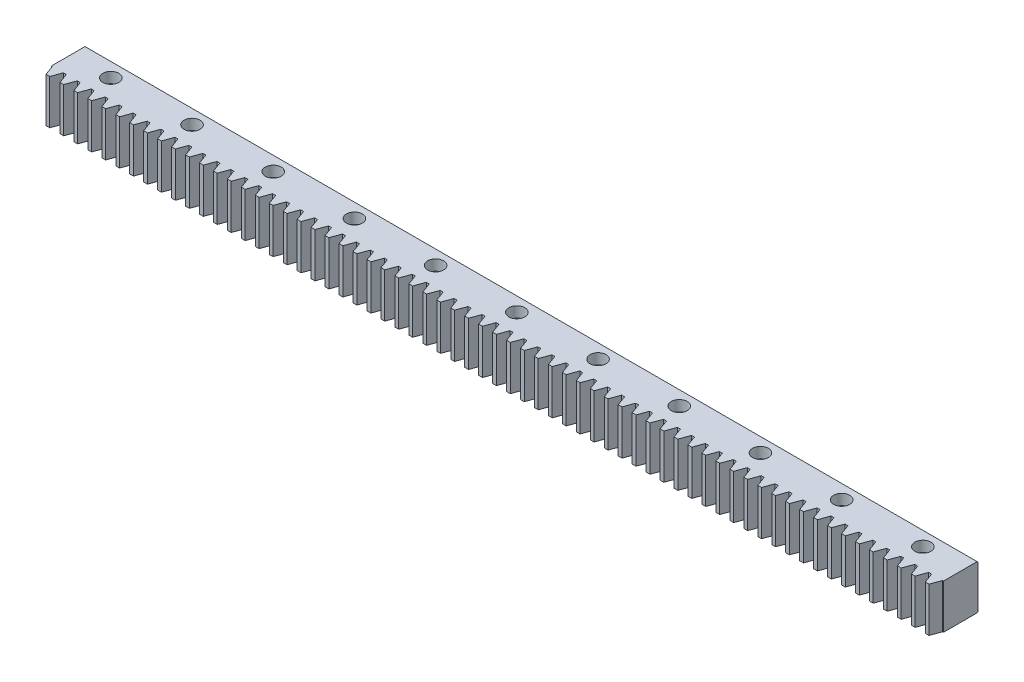
SolidWorks part; units mm, degrees
ref_plane "前基準面" through (0, 0, 0) normal (0, 0, 1) x (1, 0, 0)
ref_plane "上基準面" through (0, 0, 0) normal (0, 1, 0) x (1, 0, 0)
ref_plane "右基準面" through (0, 0, 0) normal (1, 0, 0) x (0, 0, -1)
sketch "草圖1" plane through (0, 0, 0) normal (0, 1, 0) x (1, 0, 0)
  line L1 (-502, 0) -> (502, 0)
  line L2 (-502, 0) -> (-502, -50)
  line L3 (-502, -50) -> (502, -50)
  line L4 (502, 0) -> (502, -50)
  dimension "D1" = 50
  dimension "D2" = 1004
extrude "伸長1" add sketch "草圖1" along normal mid plane 50
sketch "草圖2" plane through (0, 25, 0) normal (0, 1, 0) x (1, 0, 0)
  line L0 (496.9082, -50) -> (501.0028, -38.75)
  line L1 (-502, -50) -> (502, -50) construction
  line L2 (501.0028, -38.75) -> (504.3072, -38.75)
  line L3 (504.3072, -38.75) -> (508.4018, -50)
  line L4 (508.4018, -50) -> (496.9082, -50)
  line L6 (498.728, -45) -> (506.582, -45) construction
  line L8 (502.655, -38.75) -> (502.655, -54.3263) construction
  line L10 (502, -50) -> (502, 0) construction
  dimension "D1" = 0.655
  dimension "D2" = 40
  dimension "D3" = 5
  dimension "D4" = 11.25
  dimension "D5" = 7.854
extrude "除料-伸長1" cut sketch "草圖2" against normal up to next
pattern_linear "直線複製排列1" count 65 spacing 15.708 along (-1, 0, 0) of "除料-伸長1"
chamfer "導角1" distance 1 angle 45 2 edges at (0, -25, 0) (0, 25, 0)
hole_wizard "M10 六角承窩頭蓋螺釘的柱孔1" positions "草圖6" profile "草圖5" counterbore size "M10" standard "ISO" end condition through all
sketch "草圖6" plane through (0, 25, 0) normal (0, 1, 0) x (-1, 0, 0)
  line L3 (502, 1) -> (502, 38.75) construction
  line L4 (502, 0) -> (-502, 0) construction
  point P3 (456.96, 17)
  dimension "D1" = 17
  dimension "D4" = 45.04
sketch "草圖5" plane through (-456.96, 25, 17) normal (1, 0, 0) x (0, 0, 1)
  line L0 (0, 0) -> (0, 50)
  line L1 (0, 50) -> (5.5, 50)
  line L3 (5.5, 50) -> (5.5, 12)
  line L4 (5.5, 12) -> (9, 12)
  line L5 (9, 12) -> (9, 0)
  line L7 (9, 0) -> (0, 0)
  line L11 (0, -6.35) -> (0, 107.95) construction
  dimension "貫穿孔直徑" = 11
  dimension "貫穿孔深度" = 50
  dimension "柱孔直徑" = 18
  dimension "柱孔深度" = 12
pattern_linear "直線複製排列2" count 11 spacing 91.392 along (1, 0, 0) of "M10 六角承窩頭蓋螺釘的柱孔1"
